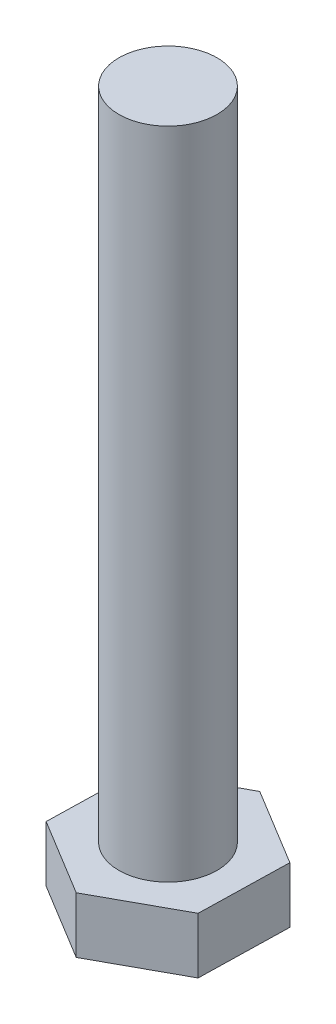
SolidWorks part; units mm, degrees
ref_plane "Спереди" through (0, 0, 0) normal (0, 0, 1) x (1, 0, 0)
ref_plane "Сверху" through (0, 0, 0) normal (0, 1, 0) x (1, 0, 0)
ref_plane "Справа" through (0, 0, 0) normal (1, 0, 0) x (0, 0, -1)
sketch "Эскиз1" plane through (0, 0, 0) normal (0, 1, 0) x (1, 0, 0)
  line L1 (9.3743, -5.6969) -> (9.6209, 5.2699)
  line L2 (9.6209, 5.2699) -> (0.2465, 10.9669)
  line L3 (0.2465, 10.9669) -> (-9.3743, 5.6969)
  line L4 (-9.3743, 5.6969) -> (-9.6209, -5.2699)
  line L5 (-9.6209, -5.2699) -> (-0.2465, -10.9669)
  line L6 (-0.2465, -10.9669) -> (9.3743, -5.6969)
  circle A0 centre (0, 0) radius 9.5 construction
extrude "Бобышка-Вытянуть1" add sketch "Эскиз1" along normal blind 8
sketch "Эскиз2" plane through (0, 8, 0) normal (0, 1, 0) x (1, 0, 0)
  circle A0 centre (0, 0) radius 6
extrude "Бобышка-Вытянуть2" add sketch "Эскиз2" along normal blind 80
chamfer "Фаска1" distance 2 angle 30 6 edges at (4.9337, 0, -8.1184) (9.4976, 0, 0.2135) (4.5639, 0, 8.3319) (-4.9337, 0, 8.1184) (-9.4976, 0, -0.2135) (-4.5639, 0, -8.3319) first distance on face at (0, 0, 0)
